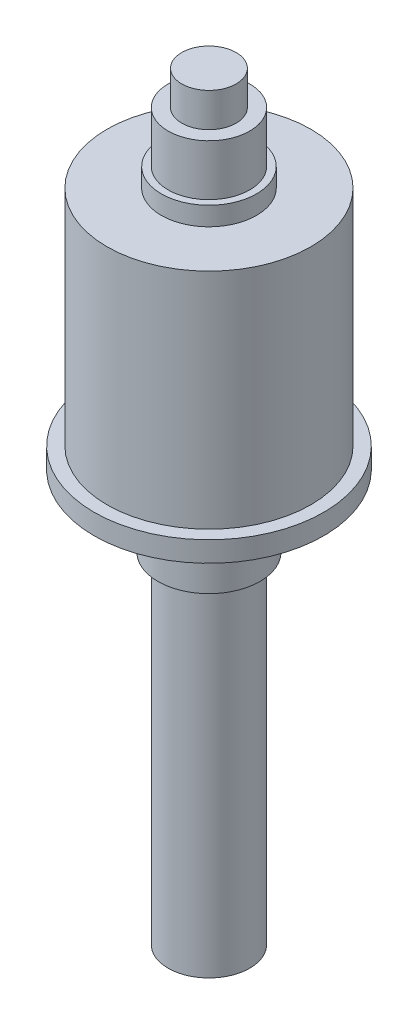
SolidWorks part; units mm, degrees
material "AISI 1035 Steel (SS)"
ref_plane "Front Plane" through (0, 0, 0) normal (0, 0, 1) x (1, 0, 0)
ref_plane "Top Plane" through (0, 0, 0) normal (0, 1, 0) x (1, 0, 0)
ref_plane "Right Plane" through (0, 0, 0) normal (1, 0, 0) x (0, 0, -1)
sketch "Sketch2" plane through (0, 0, 0) normal (0, 0, 1) x (1, 0, 0)
  line L0 (0, 40.0334) -> (0, -27.2464) construction
  line L11 (0, 0) -> (-4, 0)
  line L12 (-4, 0) -> (-4, -5)
  line L13 (-4, -5) -> (-6, -5)
  line L14 (-6, -5) -> (-6, -12.5)
  line L15 (-6, -12.5) -> (-7, -12.5)
  line L16 (-7, -12.5) -> (-7, -15.25)
  line L17 (-7, -15.25) -> (-14.9815, -15.25)
  line L18 (-14.9815, -15.25) -> (-14.9815, -48.11)
  line L26 (0, -111.61) -> (0, 0)
  line L28 (-16.8815, -51.11) -> (-16.8815, -48.11)
  line L29 (-16.8815, -48.11) -> (-14.9815, -48.11)
  line L30 (-16.8815, -51.11) -> (-9, -51.11)
  line L31 (-9, -51.11) -> (-9, -53.61)
  line L32 (-14.9815, -48.11) -> (-14.9815, -51.11) construction
  line L33 (-9, -53.61) -> (-7.5, -53.61)
  line L34 (-7.5, -53.61) -> (-7.5, -61.61)
  line L35 (-7.5, -61.61) -> (-6, -61.61)
  line L36 (-6, -61.61) -> (-6, -111.61)
  line L37 (-6, -111.61) -> (0, -111.61)
  dimension "D1" = 4
  dimension "D2" = 5
  dimension "D3" = 6
  dimension "D4" = 7.5
  dimension "D5" = 7
  dimension "D6" = 2.75
  dimension "D7" = 14.9815
  dimension "D8" = 32.86
  dimension "D10" = 3
  dimension "D11" = 9
  dimension "D12" = 2.5
  dimension "D13" = 7.5
  dimension "D14" = 8
  dimension "D15" = 6
  dimension "D16" = 50
  dimension "D9" = 1.9
revolve "Revolve1" add sketch "Sketch2" angle 360 about L0
equation "\"Stator_OD\"= 60'No Tolerance given"
equation "\"A\"=35.81 'taken off spec sheet for 06808 (A)"
equation "\"Rotor_ID\"= 30'No Tolerance Given"
equation "\"back_bearing_Thickness\"= 8'randomish, thinnest off mcmaster"
equation "\"back_bearing_OD\"= 25'currently non-sense"
equation "\"Stator_Gap\"= 0.0375'+- 0.0125 (From 1.3.3.1 Kollmorgen manual)"
equation "\"Back_mount_hole\"= 1.75'To be tapped to M2 (USE LOCKTITE)"
equation "\"facePlate_Mount_Hole\"= 5.75'To be tapped to M6"
equation "\"final_shaftD\"= 12'To fit in harmonic"
equation "\"back_bearing_ID\"= 15'Random number"
equation "\"rotor_shaftD\"= \"Rotor_ID\" - (\"rotor-shaft_gap\")*2'"
equation "\"back_bearing_IDOD\"= 18'Random number, OD of the inner bearing ring"
equation "\"final_shaftL\"= 50'random length. Idk"
equation "\"D1@Sketch2\"=4"
equation "\"D3@Sketch2\"=\"front_bearing_ID\"/2"
equation "\"D4@Sketch2\" = \"front_bearing_Thickness\" + 2.5"
equation "\"D5@Sketch2\"=\"front_bearing_IDOD\" / 2"
equation "\"D8@Sketch2\"=\"rotor_height\""
equation "\"front_bearing_ID\"= 12'random"
equation "\"front_bearing_OD\"= 20'random"
equation "\"front_bearing_IDOD\"= 14'random"
equation "\"front_bearing_Thickness\"= 5'randomish, thinnest off mcmaster"
equation "\"rotor_thickness\"= 2.4'measured off CAD"
equation "\"rotor_height\"= 32.86'+-0.075 taken off spec sheet for 06826 (C)"
equation "\"D11@Sketch2\"=\"back_bearing_IDOD\"/2"
equation "\"D13@Sketch2\"=\"back_bearing_ID\"/2"
equation "\"D14@Sketch2\"=\"back_bearing_Thickness\""
equation "\"D15@Sketch2\"=\"final_shaftD\"/2"
equation "\"D16@Sketch2\"=\"final_shaftL\""
equation "\"D9@Sketch2\"=\"rotor_thickness\"-0.5"
equation "\"rotor-shaft_gap\" = 0.0185 '+-0.0065 (from manual)"
equation "\"D7@Sketch2\"=\"Rotor_ID\"/2-\"rotor-shaft_gap\""
